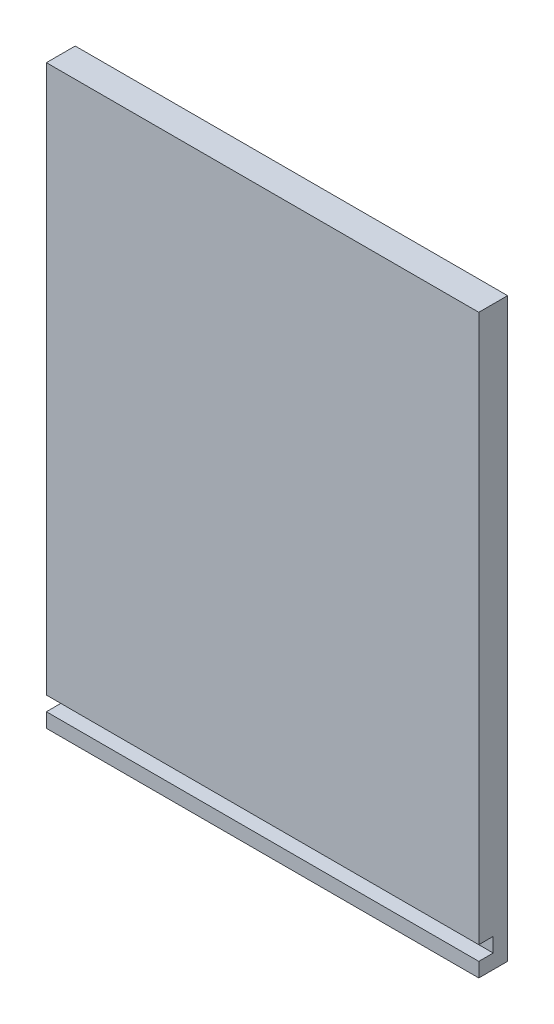
SolidWorks part; units mm, degrees
ref_plane "正面" through (0, 0, 0) normal (0, 0, 1) x (1, 0, 0)
ref_plane "平面" through (0, 0, 0) normal (0, 1, 0) x (1, 0, 0)
ref_plane "右側面" through (0, 0, 0) normal (1, 0, 0) x (0, 0, -1)
sketch "ｽｹｯﾁ1" plane through (0, 0, 0) normal (0, 0, 1) x (1, 0, 0)
  line L1 (-53.9801, 133.3357) -> (96.0199, 133.3357)
  line L2 (-53.9801, 133.3357) -> (-53.9801, -66.6643)
  line L3 (-53.9801, -66.6643) -> (96.0199, -66.6643)
  line L4 (96.0199, 133.3357) -> (96.0199, -66.6643)
  dimension "D3" = 200
  dimension "D4" = 150
extrude "ﾎﾞｽ - 押し出し1" add sketch "ｽｹｯﾁ1" along normal blind 10
sketch "ｽｹｯﾁ2" plane through (0, 0, 10) normal (0, 0, 1) x (1, 0, 0)
  line L1 (-53.9801, -56.6643) -> (96.0199, -56.6643)
  line L2 (-53.9801, -56.6643) -> (-53.9801, -61.6643)
  line L3 (-53.9801, -61.6643) -> (96.0199, -61.6643)
  line L4 (96.0199, -56.6643) -> (96.0199, -61.6643)
  line L5 (96.0199, -66.6643) -> (96.0199, 133.3357) construction
  line L7 (-53.9801, -66.6643) -> (96.0199, -66.6643) construction
  line L9 (-53.9801, 133.3357) -> (-53.9801, -66.6643) construction
  dimension "D1" = 5
  dimension "D2" = 150
  dimension "D3" = 5
extrude "ｶｯﾄ - 押し出し1" cut sketch "ｽｹｯﾁ2" against normal blind 5
